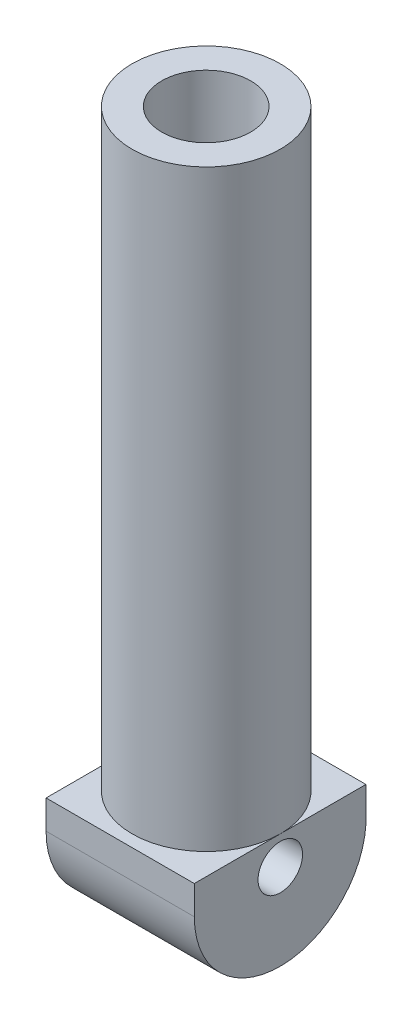
SolidWorks part; units mm, degrees
ref_plane "Front Plane" through (0, 0, 0) normal (0, 0, 1) x (1, 0, 0)
ref_plane "Top Plane" through (0, 0, 0) normal (0, 1, 0) x (1, 0, 0)
ref_plane "Right Plane" through (0, 0, 0) normal (1, 0, 0) x (0, 0, -1)
sketch "Sketch2" plane through (0, 0, 0) normal (0, 1, 0) x (1, 0, 0)
  circle A0 centre (0, 0) radius 15
  circle A1 centre (0, 0) radius 25
  dimension "D1" = 30
  dimension "D2" = 50
extrude "Boss-Extrude1" add sketch "Sketch2" along normal blind 200
ref_axis "Axis1" through (0, 210, 0) along (0, -1, 0)
ref_plane "Plane1" through (0, 0, 0) normal (-1, 0, 0) x (0, -1, 0)
sketch "Sketch5" plane through (0, 0, 0) normal (-1, 0, 0) x (0, -1, 0)
  line L0 (-210, 0) -> (10, 0) construction
  line L1 (0, 29.0121) -> (9.7062, 29.0121)
  line L2 (0, -25) -> (0, 25) construction
  line L3 (11.6287, -28.8839) -> (0, -28.8839)
  line L4 (0, -28.8839) -> (0, 29.0121)
  circle A0 centre (9.7062, 0) radius 7.5
  arc A1 (9.7062, 29.0121) -> (11.6287, -28.8839) centre (9.7062, 0.0322) cw
  dimension "D1" = 15
other "AlignGroup1"
extrude "Boss-Extrude2" add sketch "Sketch5" along normal mid plane 50
